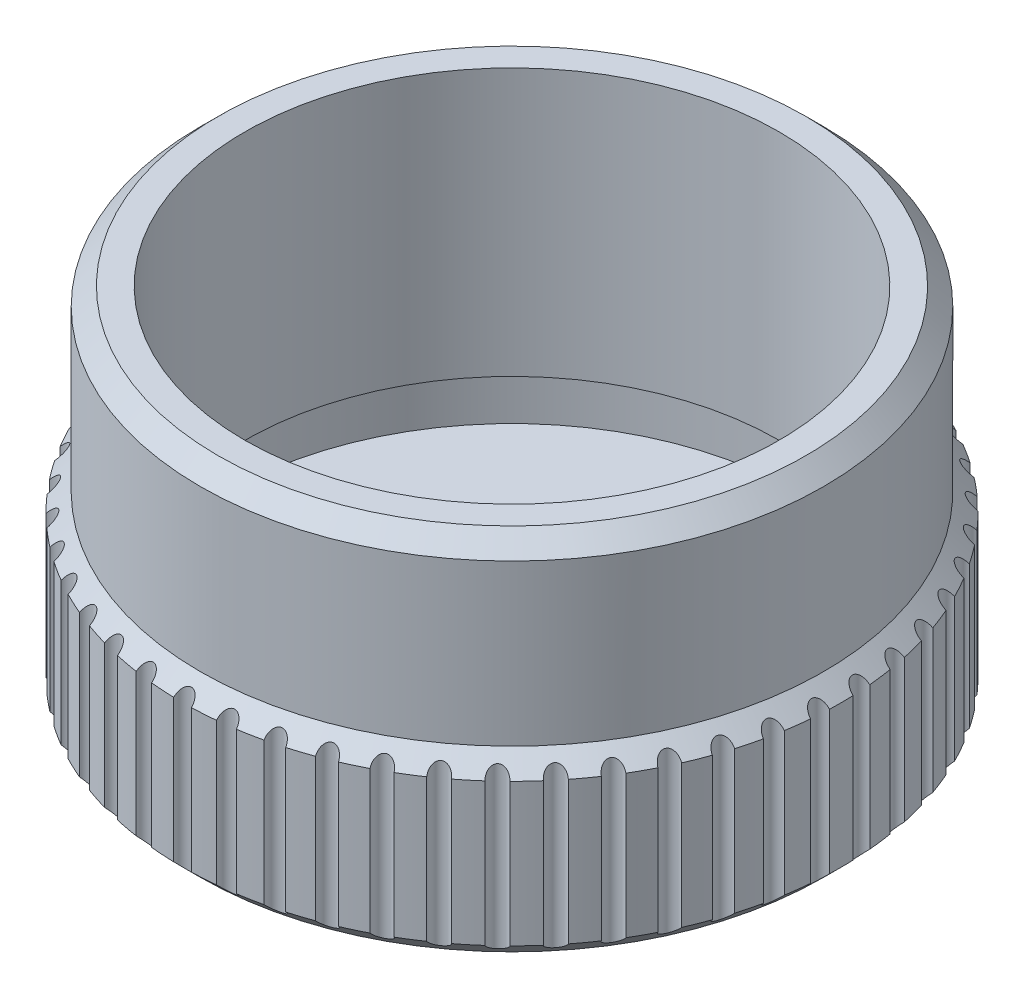
SolidWorks part; units mm, degrees
ref_plane "前视基准面" through (0, 0, 0) normal (0, 0, 1) x (1, 0, 0)
ref_plane "上视基准面" through (0, 0, 0) normal (0, 1, 0) x (1, 0, 0)
ref_plane "右视基准面" through (0, 0, 0) normal (1, 0, 0) x (0, 0, -1)
other "Configuration Table"
sketch "草图1" plane through (0, 0, 0) normal (0, 1, 0) x (1, 0, 0)
  circle A0 centre (0, 0) radius 18.5
  dimension "D1" = 37
extrude "凸台-拉伸1" add sketch "草图1" along normal blind 10
sketch "草图3" plane through (0, 10, 0) normal (0, 1, 0) x (1, 0, 0)
  circle A0 centre (0, 0) radius 17.5
  dimension "D1" = 35
extrude "凸台-拉伸2" add sketch "草图3" along normal blind 10
chamfer "倒角1" distance 1 angle 45 2 edges at (0, 0, 18.5) (0, 10, 18.5)
sketch "草图4" plane through (0, 0, 0) normal (0, -1, 0) x (1, 0, 0)
  line L0 (0, 0) -> (0, 18.5) construction
  circle A0 centre (0, 0) radius 18.5 construction
  arc A1 (0.5, 18.4932) -> (-0.5, 18.4932) centre (0, 0) ccw
  arc A2 (-0.5, 18.4932) -> (0.5, 18.4932) centre (0, 18.5) ccw
  dimension "D1" = 1
extrude "切除-拉伸1" cut sketch "草图4" against normal through all
ref_axis "基准轴1" through (0, 21, 0) along (0, -1, 0)
pattern_circular "阵列(圆周)1" count 50 over 360 about axis through (0, 21, 0) along (0, -1, 0) of "切除-拉伸1"
chamfer "倒角2" distance 1 angle 45 1 edges at (0, 20, 17.5)
sketch "草图8" plane through (0, 20, 0) normal (0, 1, 0) x (1, 0, 0)
  circle A0 centre (0, 0) radius 15
  dimension "D1" = 30
extrude "切除-拉伸2" cut sketch "草图8" against normal blind 18
sketch "草图9" plane through (0, 2, 0) normal (0, 1, 0) x (1, 0, 0)
  circle A0 centre (0, 0) radius 16
  dimension "D1" = 32
extrude "切除-拉伸3" cut sketch "草图9" along normal blind 3
